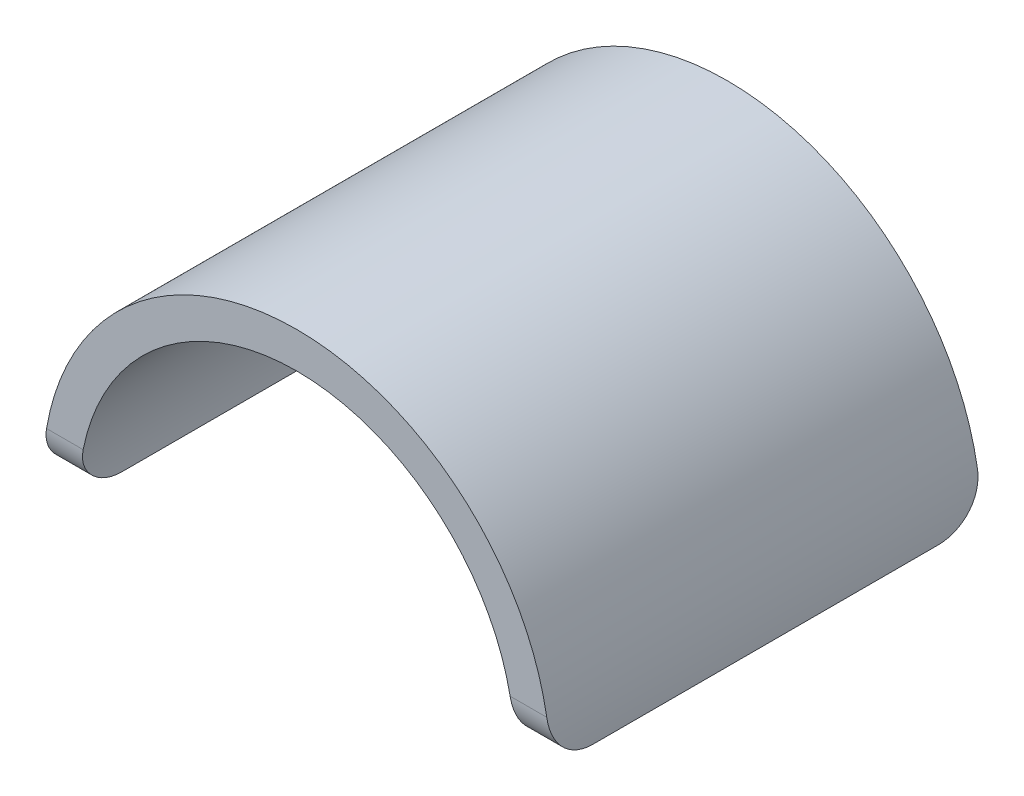
SolidWorks part; units mm, degrees
ref_plane "Piano frontale" through (0, 0, 0) normal (0, 0, 1) x (1, 0, 0)
ref_plane "Piano superiore" through (0, 0, 0) normal (0, 1, 0) x (1, 0, 0)
ref_plane "Piano destro" through (0, 0, 0) normal (1, 0, 0) x (0, 0, -1)
sketch "Schizzo1" plane through (0, 0, 0) normal (0, 0, 1) x (1, 0, 0)
  line L0 (-38.7303, 0) -> (42.7514, 0) construction
  line L3 (-29.628, 0) -> (-25.4242, 0)
  line L4 (25.4242, 0) -> (29.628, 0)
  arc A4 (25.4242, 0) -> (-25.4242, 0) centre (0, 0) ccw
  arc A5 (29.628, 0) -> (-29.628, 0) centre (0, 0) ccw
extrude "Estrusione-Estrusione2" add sketch "Schizzo1" along normal blind 50.2921
fillet "Raccordo1" radius 5 4 edges at (-27.5261, 0, 50.2921) (27.5261, 0, 50.2921) (-27.5261, 0, 0) (27.5261, 0, 0)
sketch "Schizzo9" plane through (0, 0, 0) normal (0, 0, -1) x (-1, 0, 0)
  line L0 (-24.9277, 5) -> (-29.2031, 5)
  line L1 (-29.2031, 5) -> (-24.9277, 5) construction
  line L2 (24.9277, 5) -> (29.2031, 5) construction
  line L3 (24.9277, 5) -> (29.2031, 5)
  arc A0 (-24.9277, 5) -> (24.9277, 5) centre (0, 0) cw
  arc A1 (-29.2031, 5) -> (29.2031, 5) centre (0, 0) cw
  point P6 (0, 0)
  point P8 (0, 27.5261)
  point P9 (-27.0654, 5)
  point P10 (27.0654, 5)
